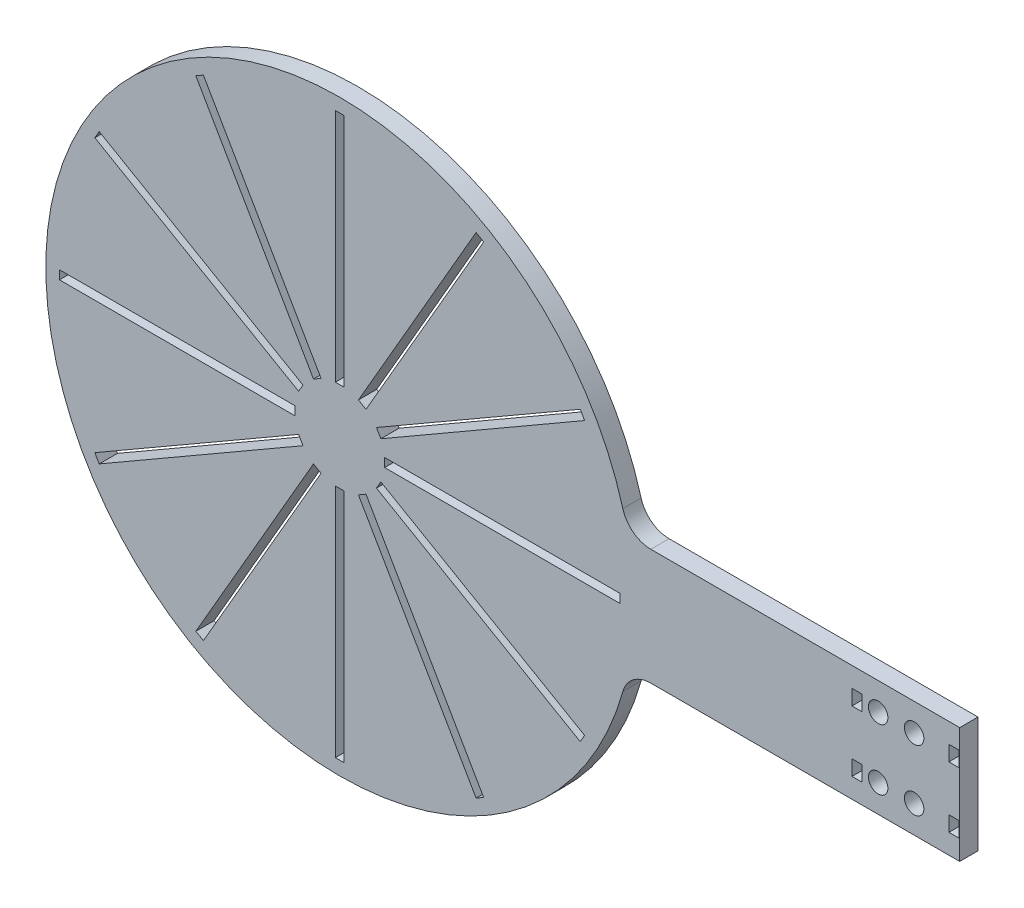
SolidWorks part; units mm, degrees
ref_plane "Front Plane" through (0, 0, 0) normal (0, 0, 1) x (1, 0, 0)
ref_plane "Top Plane" through (0, 0, 0) normal (0, 1, 0) x (1, 0, 0)
ref_plane "Right Plane" through (0, 0, 0) normal (1, 0, 0) x (0, 0, -1)
other "Configuration Table"
sketch "Sketch1" plane through (0, 0, 0) normal (0, 0, 1) x (1, 0, 0)
  circle A0 centre (0, 0) radius 96.35
  dimension "D1" = 192.7
extrude "Boss-Extrude1" add sketch "Sketch1" along normal blind 6
ref_axis "Axis1" through (0, 0, -0.635) along (0, 0, 1)
sketch "Sketch2" plane through (0, 0, 6) normal (0, 0, 1) x (1, 0, 0)
  line L0 (-1.4796, 92.05) -> (1.4796, 92.05) construction
  line L1 (-1.4796, 25.7208) -> (-1.4796, 32.8506) construction
  line L2 (1.4796, 25.7208) -> (1.4796, 32.8506) construction
  line L4 (-1.4796, 14.5354) -> (1.4796, 14.5354) construction
  line L48 (-11.8483, 8.549) -> (-78.9779, 47.3063) construction
  line L49 (-78.9779, 47.3063) -> (-80.4574, 44.7437) construction
  line L50 (-80.4574, 44.7437) -> (-13.3278, 5.9864) construction
  line L51 (-13.3278, 5.9864) -> (-11.8483, 8.549) construction
  line L52 (-14.5354, 1.4795) -> (-92.05, 1.4795) construction
  line L53 (-92.05, 1.4795) -> (-92.05, -1.4796) construction
  line L54 (-92.05, -1.4796) -> (-14.5354, -1.4796) construction
  line L55 (-14.5354, -1.4796) -> (-14.5354, 1.4795) construction
  line L56 (-13.3278, -5.9864) -> (-80.4574, -44.7437) construction
  line L57 (-80.4574, -44.7437) -> (-78.9779, -47.3063) construction
  line L58 (-78.9779, -47.3063) -> (-11.8483, -8.549) construction
  line L59 (-11.8483, -8.549) -> (-13.3278, -5.9864) construction
  line L60 (-8.549, -11.8483) -> (-47.3063, -78.9779) construction
  line L61 (-47.3063, -78.9779) -> (-44.7437, -80.4574) construction
  line L62 (-44.7437, -80.4574) -> (-5.9864, -13.3278) construction
  line L63 (-5.9864, -13.3278) -> (-8.549, -11.8483) construction
  line L64 (-1.4795, -14.5354) -> (-1.4795, -92.05) construction
  line L65 (-1.4795, -92.05) -> (1.4796, -92.05) construction
  line L66 (1.4796, -92.05) -> (1.4796, -14.5354) construction
  line L67 (1.4796, -14.5354) -> (-1.4795, -14.5354) construction
  line L68 (5.9864, -13.3278) -> (44.7437, -80.4574) construction
  line L69 (44.7437, -80.4574) -> (47.3063, -78.9779) construction
  line L70 (47.3063, -78.9779) -> (8.549, -11.8483) construction
  line L71 (8.549, -11.8483) -> (5.9864, -13.3278) construction
  line L72 (11.8483, -8.549) -> (78.9779, -47.3063) construction
  line L73 (78.9779, -47.3063) -> (80.4574, -44.7437) construction
  line L74 (80.4574, -44.7437) -> (13.3278, -5.9864) construction
  line L75 (13.3278, -5.9864) -> (11.8483, -8.549) construction
  line L76 (14.5354, -1.4795) -> (92.05, -1.4795) construction
  line L77 (92.05, -1.4795) -> (92.05, 1.4796) construction
  line L78 (92.05, 1.4796) -> (14.5354, 1.4796) construction
  line L79 (14.5354, 1.4796) -> (14.5354, -1.4795) construction
  line L80 (13.3278, 5.9864) -> (80.4574, 44.7437) construction
  line L81 (80.4574, 44.7437) -> (78.9779, 47.3063) construction
  line L82 (78.9779, 47.3063) -> (11.8483, 8.549) construction
  line L83 (11.8483, 8.549) -> (13.3278, 5.9864) construction
  line L84 (8.549, 11.8483) -> (47.3063, 78.9779) construction
  line L85 (47.3063, 78.9779) -> (44.7437, 80.4574) construction
  line L86 (44.7437, 80.4574) -> (5.9864, 13.3278) construction
  line L87 (5.9864, 13.3278) -> (8.549, 11.8483) construction
  line L88 (1.4795, 14.5354) -> (1.4796, 92.05) construction
  line L89 (1.4796, 92.05) -> (-1.4796, 92.05) construction
  line L90 (-1.4796, 92.05) -> (-1.4795, 14.5354) construction
  line L91 (-1.4795, 14.5354) -> (1.4795, 14.5354) construction
  line L92 (-5.9864, 13.3278) -> (-44.7437, 80.4574) construction
  line L93 (-44.7437, 80.4574) -> (-47.3063, 78.9779) construction
  line L94 (-47.3063, 78.9779) -> (-8.549, 11.8483) construction
  line L95 (-8.549, 11.8483) -> (-5.9864, 13.3278) construction
  line L96 (6.1229, 13.469) -> (44.6897, 80.2686)
  line L97 (-1.4319, 14.7259) -> (1.4319, 14.7259)
  line L98 (-1.4319, 14.7259) -> (-1.4319, 91.8595)
  line L99 (-1.4319, 91.8595) -> (1.4319, 91.8595)
  line L100 (1.4319, 14.7259) -> (1.4319, 91.8595)
  line L101 (6.1229, 13.469) -> (8.6031, 12.0371)
  line L102 (8.6031, 12.0371) -> (47.1698, 78.8367)
  line L103 (44.6897, 80.2686) -> (47.1698, 78.8367)
  line L104 (12.0371, 8.6031) -> (78.8367, 47.1698)
  line L105 (12.0371, 8.6031) -> (13.469, 6.1229)
  line L106 (13.469, 6.1229) -> (80.2686, 44.6897)
  line L107 (78.8367, 47.1698) -> (80.2686, 44.6897)
  line L108 (14.7259, 1.4319) -> (91.8595, 1.4319)
  line L109 (14.7259, 1.4319) -> (14.7259, -1.4319)
  line L110 (14.7259, -1.4319) -> (91.8595, -1.4319)
  line L111 (91.8595, 1.4319) -> (91.8595, -1.4319)
  line L112 (13.469, -6.1229) -> (80.2686, -44.6897)
  line L113 (13.469, -6.1229) -> (12.0371, -8.6031)
  line L114 (12.0371, -8.6031) -> (78.8367, -47.1698)
  line L115 (80.2686, -44.6897) -> (78.8367, -47.1698)
  line L116 (8.6031, -12.0371) -> (47.1698, -78.8367)
  line L117 (8.6031, -12.0371) -> (6.1229, -13.469)
  line L118 (6.1229, -13.469) -> (44.6897, -80.2686)
  line L119 (47.1698, -78.8367) -> (44.6897, -80.2686)
  line L120 (1.4319, -14.7259) -> (1.4319, -91.8595)
  line L121 (1.4319, -14.7259) -> (-1.4319, -14.7259)
  line L122 (-1.4319, -14.7259) -> (-1.4319, -91.8595)
  line L123 (1.4319, -91.8595) -> (-1.4319, -91.8595)
  line L124 (-6.1229, -13.469) -> (-44.6897, -80.2686)
  line L125 (-6.1229, -13.469) -> (-8.6031, -12.0371)
  line L126 (-8.6031, -12.0371) -> (-47.1698, -78.8367)
  line L127 (-44.6897, -80.2686) -> (-47.1698, -78.8367)
  line L128 (-12.0371, -8.6031) -> (-78.8367, -47.1698)
  line L129 (-12.0371, -8.6031) -> (-13.469, -6.1229)
  line L130 (-13.469, -6.1229) -> (-80.2686, -44.6897)
  line L131 (-78.8367, -47.1698) -> (-80.2686, -44.6897)
  line L132 (-14.7259, -1.4319) -> (-91.8595, -1.4319)
  line L133 (-14.7259, -1.4319) -> (-14.7259, 1.4319)
  line L134 (-14.7259, 1.4319) -> (-91.8595, 1.4319)
  line L135 (-91.8595, -1.4319) -> (-91.8595, 1.4319)
  line L136 (-13.469, 6.1229) -> (-80.2686, 44.6897)
  line L137 (-13.469, 6.1229) -> (-12.0371, 8.6031)
  line L138 (-12.0371, 8.6031) -> (-78.8367, 47.1698)
  line L139 (-80.2686, 44.6897) -> (-78.8367, 47.1698)
  line L140 (-8.6031, 12.0371) -> (-47.1698, 78.8367)
  line L141 (-8.6031, 12.0371) -> (-6.1229, 13.469)
  line L142 (-6.1229, 13.469) -> (-44.6897, 80.2686)
  line L143 (-47.1698, 78.8367) -> (-44.6897, 80.2686)
  point P98 (0, 0)
  dimension "D1" = 0.1905
  dimension "D2" = 0.1905
  dimension "D3" = 0.0953
  dimension "D4" = 0.0953
  dimension "D5" = 12
extrude "Cut-Extrude1" cut sketch "Sketch2" against normal through all
sketch "Sketch3" plane through (0, 0, 0) normal (0, 0, 1) x (1, 0, 0)
  line L0 (203.2, 19) -> (94.458, 19)
  line L1 (203.2, -19) -> (94.458, -19)
  line L2 (203.2, 19) -> (203.2, -19)
  line L3 (171.1278, 12.5) -> (171.1278, 7.5) construction
  line L4 (171.1278, 12.5) -> (171.1278, 7.5)
  line L5 (171.1278, -12.5) -> (171.1278, -7.5) construction
  line L6 (171.1278, -12.5) -> (171.1278, -7.5)
  line L7 (202.8923, 12.5) -> (202.8923, 7.5) construction
  line L8 (202.8923, -12.5) -> (202.8923, -7.5) construction
  line L9 (202.8923, 12.5) -> (202.8923, 7.5)
  line L10 (202.8923, -12.5) -> (202.8923, -7.5)
  line L11 (167.9, 12.5) -> (167.9, 7.5) construction
  line L12 (167.9, -12.5) -> (167.9, -7.5) construction
  line L13 (199.6645, -12.5) -> (199.6645, -7.5) construction
  line L14 (199.6645, 12.5) -> (199.6645, 7.5) construction
  line L15 (167.9, 12.5) -> (167.9, 7.5)
  line L16 (167.9, -12.5) -> (167.9, -7.5)
  line L17 (199.6645, -12.5) -> (199.6645, -7.5)
  line L18 (199.6645, 12.5) -> (199.6645, 7.5)
  line L19 (167.9, 12.5) -> (171.1278, 12.5)
  line L20 (171.1278, 7.5) -> (167.9, 7.5)
  line L21 (167.9, -7.5) -> (171.1278, -7.5)
  line L22 (167.9, -12.5) -> (171.1278, -12.5)
  line L23 (199.6645, -12.5) -> (202.8923, -12.5)
  line L24 (202.8923, -7.5) -> (199.6645, -7.5)
  line L25 (199.6645, 12.5) -> (202.8923, 12.5)
  line L26 (202.8923, 7.5) -> (199.6645, 7.5)
  line L27 (173.7, 10) -> (196.836, 10) construction
  line L28 (173.7, 7.25) -> (173.7, 12.75) construction
  line L29 (196.836, 7.25) -> (196.836, 12.75) construction
  line L30 (173.7, -10) -> (196.836, -10) construction
  line L31 (173.7, -7.25) -> (173.7, -12.75) construction
  line L32 (196.836, -7.25) -> (196.836, -12.75) construction
  circle A0 centre (0, 0) radius 96.35 construction
  arc A1 (94.458, -19) -> (94.458, 19) centre (0, 0) ccw
  dimension "D1" = 94.458
  dimension "D2" = 203.2
extrude "Boss-Extrude2" add sketch "Sketch3" along normal up to surface (6 mm away) up to face at (-26.6464, -46.1529, 6)
fillet "Fillet1" radius 9.525 2 edges at (94.458, -19, 3) (94.458, 19, 3)
sketch "Sketch4" plane through (0, 0, 6) normal (0, 0, 1) x (1, 0, 0)
  circle A0 centre (0, 0) radius 4.8704
  circle A1 centre (0, 0) radius 1.27
  dimension "D1" = 9.7409
  dimension "D2" = 2.54
sketch "Sketch5" plane through (0, 0, 6) normal (0, 0, 1) x (1, 0, 0)
  point P0 (188.2589, -10)
  point P2 (176.4735, -10)
  point P4 (176.4735, 10)
  point P6 (188.2589, 10)
hole_wizard "Ø6.4 (6.4) Diameter Hole1" positions "Sketch5" profile "Sketch6" hole size "Ø6.4" standard "ANSI Metric" end condition through all
sketch "Sketch6" plane through (188.2589, -10, 6) normal (1, 0, 0) x (0, -1, 0)
  line L0 (0, 0) -> (0, 6)
  line L1 (0, 6) -> (3.2, 6)
  line L2 (3.2, 6) -> (3.2, 0)
  line L5 (3.2, 0) -> (0, 0)
  line L11 (0, -6.35) -> (0, 107.95) construction
  dimension "Thru Hole Dia." = 6.4
  dimension "Thru Hole Depth" = 6
equation "\"wire gauge\"= 14"
equation "\"wire diameter\"= 0.005 * 92 ^ ( ( 36 - \"wire gauge\" ) / 39 ) * 1in"
equation "\"wire diameter with insulation\"= 0.0682 * 1in"
equation "\"insulation thickness\"= ( \"wire diameter with insulation\" - \"wire diameter\" ) / 2 * 1in"
equation "\"bend radius\"= \"wire diameter with insulation\" * 3"
equation "\"inner diameter\"= 36 * 1mm"
equation "\"outer diameter\"= 180 * 1mm"
equation "\"turns\"= 8"
equation "\"pitch\"= ( \"outer diameter\" - \"inner diameter\" ) / \"turns\" / 2"
equation "\"D1@Sketch1\"=\"outer diameter\"+0.5"
